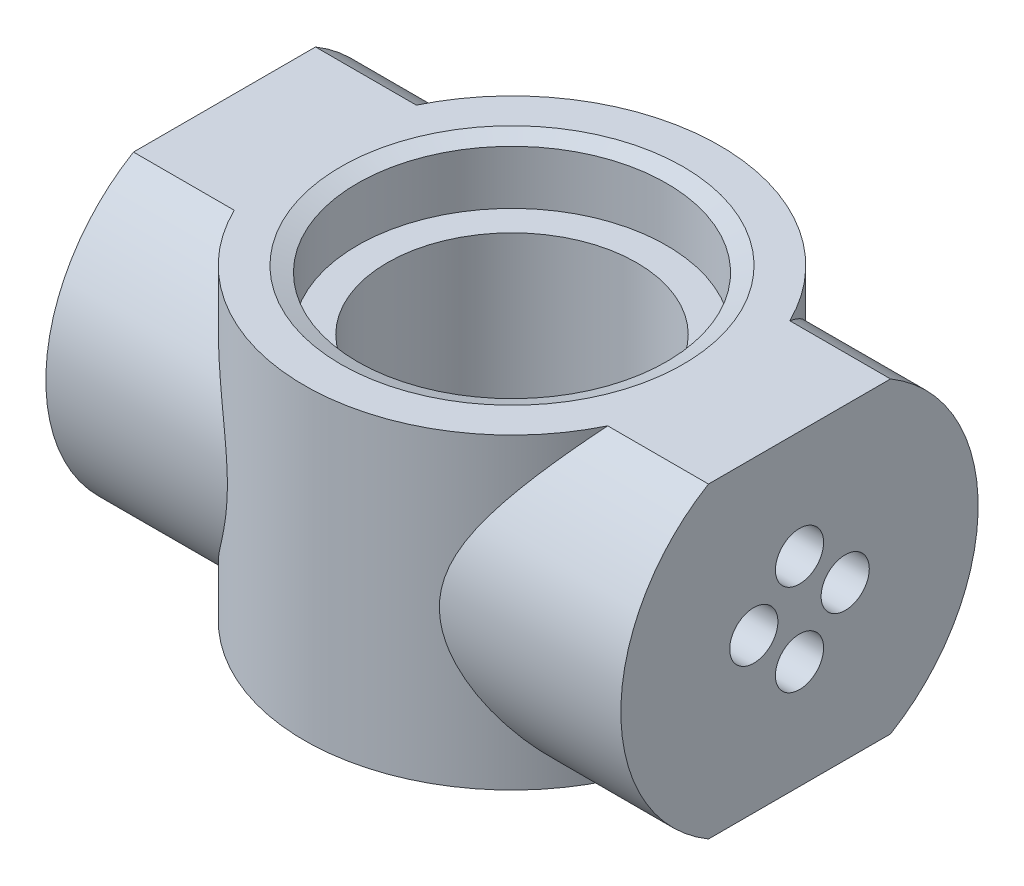
SolidWorks part; units mm, degrees
ref_plane "Ebene vorne" through (0, 0, 0) normal (0, 0, 1) x (1, 0, 0)
ref_plane "Ebene oben" through (0, 0, 0) normal (0, 1, 0) x (1, 0, 0)
ref_plane "Ebene rechts" through (0, 0, 0) normal (1, 0, 0) x (0, 0, -1)
ref_plane "Ebene1" through (18.6, 0, 0) normal (1, 0, 0) x (0, 0, -1)
sketch "Skizze1" plane through (0, 0, 0) normal (0, 1, 0) x (1, 0, 0)
  circle A0 centre (0, 0) radius 25
  circle A1 centre (0, 0) radius 18.6
  dimension "D1" = 50
  dimension "D2" = 37.2
extrude "Aufsatz-Linear austragen1" add sketch "Skizze1" along normal mid plane 37
sketch "Skizze2" plane through (0, 0, 0) normal (0, 1, 0) x (1, 0, 0)
  circle A0 centre (0, 0) radius 15
  circle A5 centre (0, 0) radius 18.6
  circle A6 centre (0, 0) radius 18.6 construction
  dimension "D2" = 30
extrude "Aufsatz-Linear austragen2" add sketch "Skizze2" along normal mid plane 22.6
sketch "Skizze3" plane through (18.6, 0, 0) normal (1, 0, 0) x (0, 0, -1)
  line L9 (-25, -18.5) -> (25, -18.5) construction
  circle A2 centre (0, 0) radius 21.5
  dimension "D1" = 3
extrude "Aufsatz-Linear austragen3" add sketch "Skizze3" along normal blind 16
sketch "Skizze4" plane through (34.6, 0, 0) normal (1, 0, 0) x (0, 0, -1)
  line L0 (0, 0) -> (-5.5, 0) construction
  circle A0 centre (-5.5, 0) radius 2.9
  circle A1 centre (0, 5.5) radius 2.9
  circle A2 centre (5.5, 0) radius 2.9
  circle A3 centre (0, -5.5) radius 2.9
  point P13 (0, 0)
  dimension "D2" = 5.8
  dimension "D1" = 5.5
  dimension "D3" = 4
extrude "Schnitt-Linear austragen1" cut sketch "Skizze4" against normal blind 9.1
mirror "Spiegeln1" about plane through (0, 0, 0) normal (1, 0, 0) of "Schnitt-Linear austragen1", "Aufsatz-Linear austragen3"
sketch "Skizze5" plane through (0, 29.286, 0) normal (-1, 0, 0) x (0, -1, 0)
  line L1 (10.786, 25) -> (47.786, 25)
  line L2 (10.786, 25) -> (10.786, -25)
  line L3 (10.786, -25) -> (47.786, -25)
  line L4 (47.786, 25) -> (47.786, -25)
  line L5 (47.786, 25) -> (10.786, 25) construction
  line L6 (10.786, 25) -> (10.786, 10.9545) construction
extrude "Schnitt-Linear austragen2" cut sketch "Skizze5" against normal through all both and the other way through all flip side to cut
ref_axis "Achse1" through (31.35, 0, 0) along (-1, 0, 0)
ref_axis "Achse2" through (0, -20.35, 0) along (0, 1, 0)
sketch "Skizze7" plane through (18.6, 0, 0) normal (-1, 0, 0) x (0, 0, 1)
  line L0 (16.7045, 13.5355) -> (16.7045, -13.5355)
  line L1 (16.7045, 13.5355) -> (16.7045, -13.5355) construction
  arc A0 (16.7045, -13.5355) -> (16.7045, 13.5355) centre (0, 0) ccw construction
  arc A1 (16.7045, -13.5355) -> (16.7045, 13.5355) centre (0, 0) ccw
extrude "Aufsatz-Linear austragen4" add sketch "Skizze7" along normal up to surface (37.2 mm away)
mirror "Spiegeln2" about plane through (0, 0, 0) normal (0, 0, 1) of "Aufsatz-Linear austragen4"
sketch "Skizze8" plane through (0, 11.3, 0) normal (0, 1, 0) x (1, 0, 0)
  circle A1 centre (0, 0) radius 18.6
  circle A2 centre (0, 0) radius 18.6
  dimension "D1" = 0
extrude "Schnitt-Linear austragen3" cut sketch "Skizze8" along normal through all
mirror "Spiegeln3" about plane through (0, 0, 0) normal (0, 1, 0) of "Schnitt-Linear austragen3"
chamfer "Fase1" distance 2 angle 20 2 edges at (0, 18.5, 18.6) (0, -18.5, 18.6) first distance on face at (0, 18.5, 0) first distance on face at (0, -11.3, 18.6)
